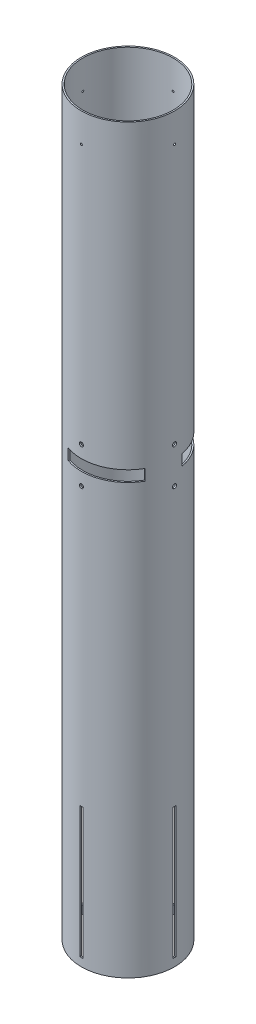
SolidWorks part; units mm, degrees
material "A-Glass Fiber"
ref_plane "Front Plane" through (0, 0, 0) normal (0, 0, 1) x (1, 0, 0)
ref_plane "Top Plane" through (0, 0, 0) normal (0, 1, 0) x (1, 0, 0)
ref_plane "Right Plane" through (0, 0, 0) normal (1, 0, 0) x (0, 0, -1)
sketch "Sketch1" plane through (0, 0, 0) normal (0, 1, 0) x (1, 0, 0)
  circle A0 centre (0, 0) radius 49.53
  circle A1 centre (0, 0) radius 51.1048
  dimension "D1" = 99.06
  dimension "D2" = 102.2096
extrude "Boss-Extrude1" add sketch "Sketch1" along normal blind 812.8
ref_plane "Plane1" through (0, 0, 0) normal (0.7071, 0, 0.7071) x (0.7071, 0, -0.7071)
ref_axis "Axis1" through (0, 812.8, 0) along (0, -1, 0)
sketch "Sketch2" plane through (0, 0, 0) normal (1, 0, 0) x (0, 0, -1)
  line L0 (0, 0) -> (0, 8.89)
  line L1 (1.5875, 8.89) -> (-1.5875, 8.89)
  line L2 (1.5875, 8.89) -> (1.5875, 152.4)
  line L3 (1.5875, 152.4) -> (-1.5875, 152.4)
  line L4 (-1.5875, 8.89) -> (-1.5875, 152.4)
  line L5 (1.5875, 8.89) -> (-1.5875, 152.4) construction
  line L6 (1.5875, 152.4) -> (-1.5875, 8.89) construction
  line L7 (51.1048, 812.8) -> (-51.1048, 812.8) construction
  line L8 (51.1048, 812.8) -> (-51.1048, 812.8)
  line L9 (0, 812.8) -> (0, 496.188)
  line L10 (-51.1048, 0) -> (51.1048, 0) construction
  circle A0 centre (0, 496.188) radius 2.25
  point P0 (0, 80.645)
  dimension "D4" = 4.5
  dimension "D1" = 3.175
  dimension "D5" = 496.188
  dimension "D3" = 152.4
  dimension "D2" = 8.89
extrude "Cut-Extrude1" cut sketch "Sketch2" against normal through all contours L4 L1 L2 L3 region at (0, 80.645, 0)
pattern_circular "CirPattern1" count 4 over 360 about axis through (0, 0, 0) along (0, 1, 0) of "Cut-Extrude1" reverse direction yes
extrude "Cut-Extrude2" cut sketch "Sketch2<3>" against normal through all contours A0 region at (0, 494.642, 1.546)
sketch "Sketch2<3>" plane through (0, 0, 0) normal (1, 0, 0) x (0, 0, -1) same geometry as "Sketch2"
pattern_circular "CirPattern2" count 4 over 360 about axis through (0, 812.8, 0) along (0, -1, 0) of "Cut-Extrude2"
sketch "Sketch3" plane through (0, 0, 0) normal (0.7071, 0, 0.7071) x (0.7071, 0, -0.7071)
  line L0 (0, 0) -> (0, 127) construction
  circle A0 centre (0, 127) radius 3.175
  dimension "D1" = 6.35
  dimension "D2" = 127
extrude "Cut-Extrude3" cut sketch "Sketch3" against normal through all
sketch "Sketch7" plane through (0, 0, 0) normal (0, 1, 0) x (1, 0, 0)
  line L0 (0, 0) -> (-44.2581, -25.5524)
  line L1 (0, 0) -> (0, 93.232) construction
  line L2 (0, 0) -> (-32.8495, 39.1485)
  line L3 (-51.1048, 0) -> (0, 0) construction
  arc A0 (-51.0552, 2.25) -> (-51.0552, -2.25) centre (0, 0) ccw construction
  circle A1 centre (0, 0) radius 49.53 construction
  circle A2 centre (0, 0) radius 51.1048
  circle A3 centre (0, 0) radius 51.1048
  circle A4 centre (0, 0) radius 49.53
  circle A5 centre (0, 0) radius 51.1048 construction
  arc A6 (2.25, 51.0552) -> (-2.25, 51.0552) centre (0, 0) ccw construction
  arc A7 (-51.0552, 2.25) -> (-51.0552, -2.25) centre (0, 0) ccw
  arc A8 (2.25, 51.0552) -> (-2.25, 51.0552) centre (0, 0) ccw
  dimension "D1" = 80
  dimension "D3" = 30
  dimension "D2" = 0
extrude "Cut-Extrude4" cut sketch "Sketch7" against normal blind 12.065 from offset 482.6 contours A4 A3 L0 region at (-43.9137, 0, 24.5741)
pattern_circular "CirPattern3" count 3 over 360 about axis through (0, 812.8, 0) along (0, -1, 0) of "Cut-Extrude4"
pattern_linear "LPattern1" count 2 spacing 39.6916 along (0, -1, 0) of "CirPattern2"
sketch "Sketch8" plane through (0, 0, 0) normal (0, 0, 1) x (1, 0, 0)
  line L0 (49.53, 812.8) -> (-49.53, 812.8) construction
  circle A0 centre (0, 781.05) radius 1.0922
  dimension "D1" = 2.1844
  dimension "D2" = 31.75
extrude "Cut-Extrude5" cut sketch "Sketch8" against normal through all
pattern_circular "CirPattern4" count 4 over 360 about axis through (0, 812.8, 0) along (0, -1, 0) of "Cut-Extrude5"
sketch "Sketch9" plane through (0, 0, 0) normal (0, 0, 1) x (1, 0, 0)
  line L0 (51.1048, 812.8) -> (-51.1048, 812.8) construction
  point P0 (0, 752.856)
  dimension "D1" = 59.944
hole_wizard "1/2 Clearance Hole4" positions "Sketch17" profile "Sketch18" hole size "1/2" standard "ANSI Inch" end condition through all
sketch "Sketch17" plane through (0, 0, 0) normal (0, 0, 1) x (1, 0, 0)
  line L0 (51.1048, 812.8) -> (-51.1048, 812.8) construction
  point P0 (0, 752.856)
  dimension "D1" = 752.856
  dimension "D2" = 59.944
sketch "Sketch18" plane through (0, 752.856, 0) normal (1, 0, 0) x (0, -1, 0)
  line L0 (0, 0) -> (0, 51.1048)
  line L1 (0, 51.1048) -> (6.5481, 51.1048)
  line L2 (6.5481, 51.1048) -> (6.5481, 0)
  line L5 (6.5481, 0) -> (0, 0)
  line L11 (0, -6.35) -> (0, 107.95) construction
  dimension "Thru Hole Dia." = 13.0962
  dimension "Thru Hole Depth" = 51.1048
ref_plane "Plane3" through (24.3888, 0, -29.0654) normal (0.6428, 0, -0.766) x (-0.766, 0, -0.6428)
equation "\"D1@Boss-Extrude1\" = \"Aft_Section_Length\""
equation "\"AB_Coupler_OD_Length\"= 1in"
equation "\"AB_Coupling_Section_Length\"= 0.375in"
equation "\"AB_Coupler_Length\"= \"AB_Coupler_OD_Length\" + \"AB_Coupling_Section_Length\" * 2"
equation "\"AB_Coupler_Num_Screws\"= 4"
equation "\"AB_Coupling_Screw_Diameter\"= 4.5mm"
equation "\"Aft_Section_Length\" = 32in"
equation "\"D4@Sketch2\"=\"AB_Coupling_Screw_Diameter\""
equation "\"D1@CirPattern2\"=\"AB_Coupler_Num_Screws\""
equation "\"Rail_Nut_From_Bottom\"= 5in"
equation "\"Rail_Nut_Diam\"= 0.25in"
equation "\"D1@Sketch3\"=\"Rail_Nut_Diam\""
equation "\"D2@Sketch3\"=\"Rail_Nut_From_Bottom\""
equation "\"AB_BKHD_Thickness\"= 0.375in"
equation "\"AB_Mount_From_Bottom\"= 19.25in"
equation "\"Cutout_Angle\" = 60"
equation "\"Motor_OD\" = 54.4mm"
equation "\"Motor_Length\" = 401mm"
equation "\"Mid_Coupler_Length\" = 12in"
equation "\"AB_Paddle_Height\" = 0.375in"
equation "\"Num_Cutouts\" = 4"
equation "\"AB_Coupler_OD\"= 4.024in"
equation "\"AB_Coupler_ID\"= 3.7in"
equation "\"AB_Coupler_Surface_Diameter\"= 3.899in"
equation "\"AB_Central_Bushing_Length\" = 0.75in"
equation "\"Lead_Screw_Dist\" = 2in"
equation "\"Lead_Screw_Diam\" = 0.375in"
equation "\"Lead_Screw_Length\" = \"Mid_Coupler_Length\" + 2*0.375in + 2*0.5in"
equation "\"Paddle_Pin_Offset\" = 0.25in"
equation "\"Paddle_Pin_Radius\" = 2.25*2/3in"
equation "\"Paddle_Gear_OD\" = 3.2in"
equation "\"Fwd_BKHD_From_Top\" = 18in"
equation "\"Body_Tube_OD\"= 4.024in"
equation "\"Body_Tube_ID\"= 3.90in"
equation "\"Coupler_OD\" = 3.899in"
equation "\"Coupler_ID\" = 3.755in"
equation "\"Fwd_Section_Length\" = 20in"
equation "\"Mid_Section_Length\" = 4in"
equation "\"Aft_Upper_Tube_Length\" = 10in"
equation "\"Aft_Lower_Tube_Length\" = 18in"
equation "\"Nosecone_Coupler_Length\" = 5in"
equation "\"Avionics_Bulkhead_Thickness\" = 0.25in"
equation "\"Avionics_Bulkhead_Lip\" = 0.125in"
equation "\"Avionics_Board_Length\" = \"Mid_Coupler_Length\" - 2*\"Avionics_Bulkhead_Lip\""
equation "\"Lead_Screw_Hole_Diam\" = 0.386in"
equation "\"Centering_Ring_Cutout_Dia\"= 1in"
equation "\"D2@Sketch1\"=\"Body_Tube_OD\""
equation "\"D1@Sketch1\"=\"Body_Tube_ID\""
equation "\"D5@Sketch2\"=\"AB_Mount_From_Bottom\"+0.393701-0.0787402-.03"
equation "\"D19@Cut-Extrude4\"=\"AB_Mount_From_Bottom\"-0.25"
